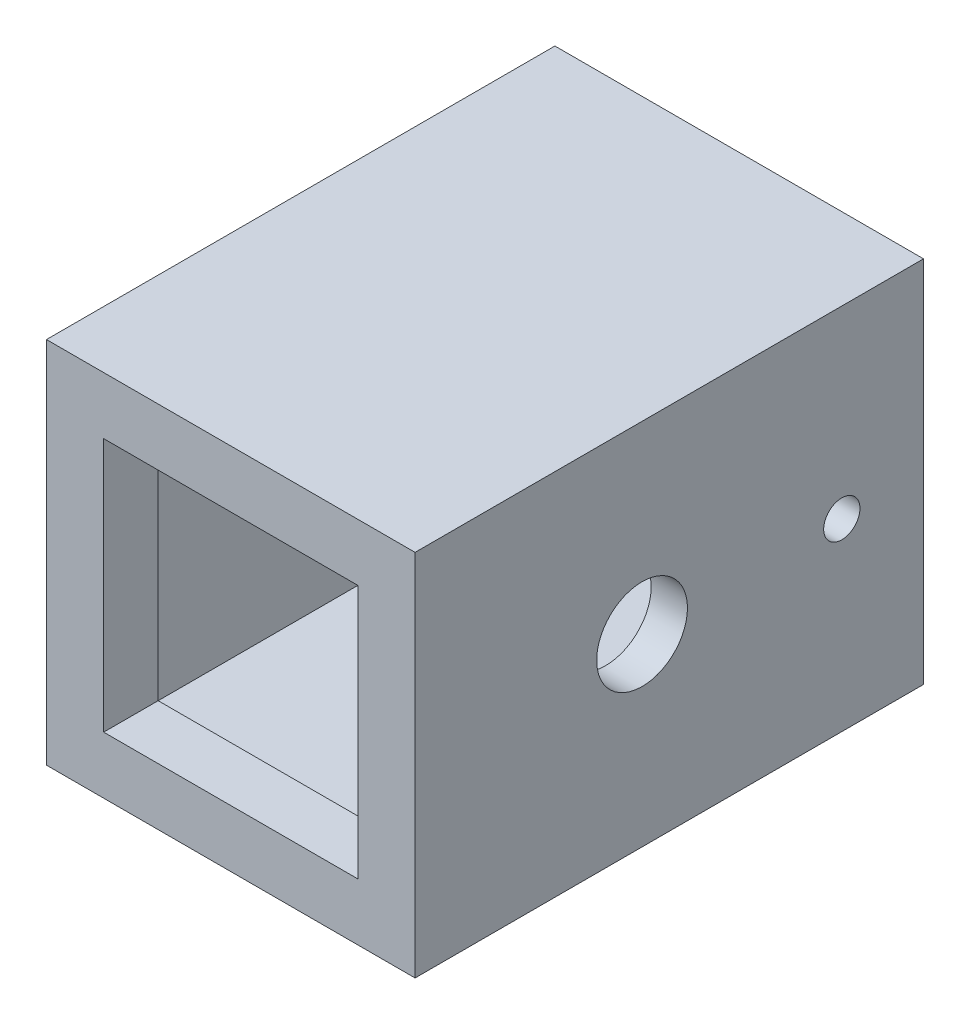
SolidWorks part; units mm, degrees
ref_plane "Front Plane" through (0, 0, 0) normal (0, 0, 1) x (1, 0, 0)
ref_plane "Top Plane" through (0, 0, 0) normal (0, 1, 0) x (1, 0, 0)
ref_plane "Right Plane" through (0, 0, 0) normal (1, 0, 0) x (0, 0, -1)
ref_axis "Axis1" through (0, 0, 0.5) along (0, 0, -1)
sketch "Sketch1" plane through (0, 0, 0) normal (0, 0, 1) x (1, 0, 0)
  line L5 (-10.15, -10.15) -> (10.15, -10.15)
  line L14 (-10.15, -10.15) -> (-10.15, 10.15)
  line L15 (-10.15, 10.15) -> (10.15, 10.15)
  line L16 (10.15, -10.15) -> (10.15, 10.15)
  line L17 (-10.15, -10.15) -> (10.15, 10.15) construction
  line L18 (-10.15, 10.15) -> (10.15, -10.15) construction
  line L19 (-8.15, -8.15) -> (8.15, -8.15)
  line L20 (-8.15, -8.15) -> (-8.15, 8.15)
  line L21 (-8.15, 8.15) -> (8.15, 8.15)
  line L22 (8.15, -8.15) -> (8.15, 8.15)
  line L23 (-8.15, -8.15) -> (8.15, 8.15) construction
  line L24 (-8.15, 8.15) -> (8.15, -8.15) construction
  point P0 (0, 0)
  point P6 (0, 0)
  dimension "D1" = 16.3
  dimension "D2" = 2
extrude "Boss-Extrude1" add sketch "Sketch1" against normal blind 25
sketch "Sketch2" plane through (0, 0, 0) normal (0, 0, 1) x (1, 0, 0)
  line L1 (10.15, 10.15) -> (-10.15, 10.15)
  line L2 (10.15, 10.15) -> (10.15, -10.15)
  line L3 (10.15, -10.15) -> (-10.15, -10.15)
  line L4 (-10.15, 10.15) -> (-10.15, -10.15)
  line L5 (-7, -7) -> (7, -7)
  line L6 (-7, -7) -> (-7, 7)
  line L7 (-7, 7) -> (7, 7)
  line L8 (7, -7) -> (7, 7)
  line L9 (-7, -7) -> (7, 7) construction
  line L10 (-7, 7) -> (7, -7) construction
  point P4 (0, 0)
extrude "Boss-Extrude2" add sketch "Sketch2" along normal blind 3
sketch "Sketch3" plane through (10.15, 0, 0) normal (1, 0, 0) x (0, 0, -1)
  arc A0 (6.4381, 5.875) -> (6.4381, -5.875) centre (9.5, 0) ccw construction
  arc A1 (6.4381, 5.875) -> (6.4381, -5.875) centre (9.5, 0) ccw construction
  circle A2 centre (20.5, 0) radius 3 construction
  circle A3 centre (20.5, 0) radius 3 construction
  circle A4 centre (20.5, 0) radius 1
  circle A6 centre (9.5, 0) radius 2.5
  dimension "D1" = 2
  dimension "D2" = 5
extrude "Cut-Extrude1" cut sketch "Sketch3" against normal through all
fillet "Fillet1" radius 1 4 edges at (-8.15, 0, -25) (0, -8.15, -25) (8.15, 0, -25) (0, 8.15, -25)
